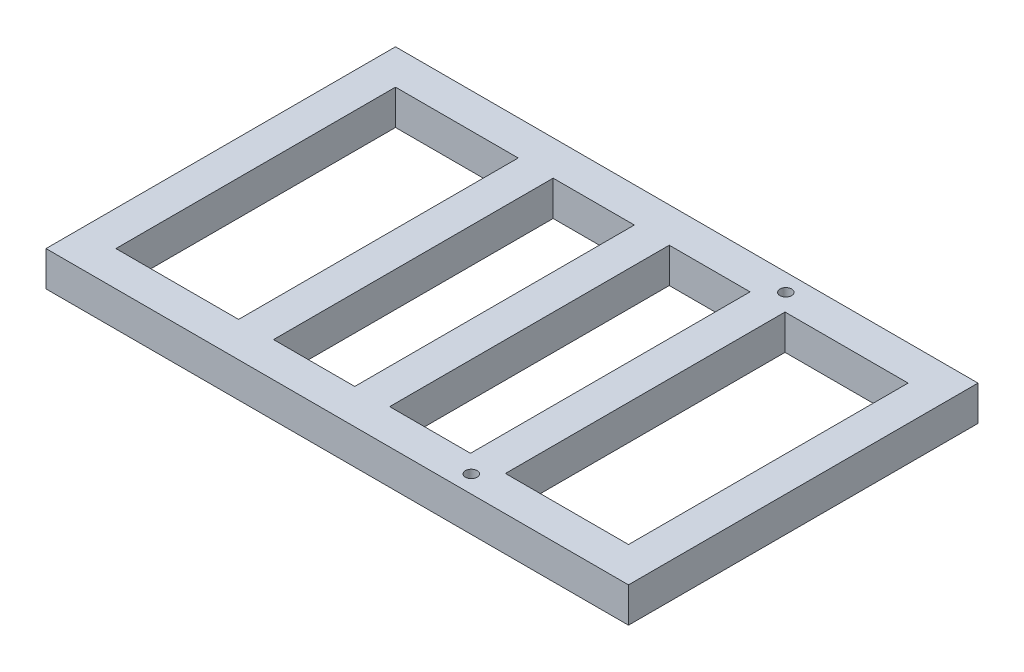
SolidWorks part; units mm, degrees
ref_plane "Front Plane" through (0, 0, 0) normal (0, 0, 1) x (1, 0, 0)
ref_plane "Top Plane" through (0, 0, 0) normal (0, 1, 0) x (1, 0, 0)
ref_plane "Right Plane" through (0, 0, 0) normal (1, 0, 0) x (0, 0, -1)
sketch "Sketch2" plane through (0, 0, 0) normal (0, 1, 0) x (1, 0, 0)
  line L0 (-55, 0) -> (55, 0) construction
  line L1 (-220, 120) -> (220, 120)
  line L2 (-220, 120) -> (-220, -120)
  line L3 (-220, -120) -> (220, -120)
  line L4 (220, 120) -> (220, -120)
  line L5 (-220, 120) -> (220, -120) construction
  line L6 (-220, -120) -> (220, 120) construction
  line L7 (0, -55) -> (0, 55) construction
  line L9 (-250, 150) -> (250, 150)
  line L10 (-250, 150) -> (-250, -150)
  line L11 (-250, -150) -> (250, -150)
  line L12 (250, 150) -> (250, -150)
  line L13 (-250, 150) -> (250, -150) construction
  line L14 (-250, -150) -> (250, 150) construction
  point P0 (0, 0)
  point P9 (0, 0)
  dimension "D1" = 30
  dimension "D2" = 30
  dimension "D3" = 30
  dimension "D4" = 30
  dimension "D5" = 500
  dimension "D6" = 300
extrude "Boss-Extrude1" add sketch "Sketch2" along normal blind 30
sketch "Sketch3" plane through (0, 30, 0) normal (0, 1, 0) x (1, 0, 0)
  line L0 (0, -16.5) -> (0, 16.5) construction
  line L1 (-15, 120) -> (15, 120)
  line L2 (-15, 120) -> (-15, -120)
  line L3 (-15, -120) -> (15, -120)
  line L4 (15, 120) -> (15, -120)
  line L5 (-15, 120) -> (15, -120) construction
  line L6 (-15, -120) -> (15, 120) construction
  line L7 (-16.5, 0) -> (16.5, 0) construction
  line L8 (-220, -120) -> (220, -120) construction
  point P0 (0, 0)
  dimension "D1" = 30
extrude "Boss-Extrude2" add sketch "Sketch3" against normal up to vertex (30 mm away) up to point (-250, 0, 150)
sketch "Sketch4" plane through (0, 30, 0) normal (0, 1, 0) x (1, 0, 0)
  line L0 (-16.5, 0) -> (16.5, 0) construction
  line L1 (-114.681, -120) -> (-84.681, -120)
  line L2 (-114.681, -120) -> (-114.681, 120)
  line L3 (-114.681, 120) -> (-84.681, 120)
  line L4 (-84.681, -120) -> (-84.681, 120)
  line L5 (-114.681, -120) -> (-84.681, 120) construction
  line L6 (-114.681, 120) -> (-84.681, -120) construction
  line L7 (-15, 120) -> (-220, 120) construction
  line L8 (220, 120) -> (15, 120) construction
  line L9 (84.3653, -120) -> (114.3653, -120)
  line L10 (84.3653, -120) -> (84.3653, 120)
  line L11 (84.3653, 120) -> (114.3653, 120)
  line L12 (114.3653, -120) -> (114.3653, 120)
  line L13 (84.3653, -120) -> (114.3653, 120) construction
  line L14 (84.3653, 120) -> (114.3653, -120) construction
  point P0 (-99.681, 0)
  point P9 (99.3653, 0)
  dimension "D1" = 30
  dimension "D2" = 30
sketch "Sketch7" plane through (0, 0, 0) normal (0, 1, 0) x (1, 0, 0)
extrude "Boss-Extrude3" add sketch "Sketch4" against normal up to vertex (30 mm away) up to point (-250, 0, 150)
sketch "Sketch8" plane through (0, 30, 0) normal (0, 1, 0) x (1, 0, 0)
  line L2 (250, 150) -> (-250, 150) construction
  circle A1 centre (100.0184, 135) radius 5
  dimension "D1" = 10
  dimension "D2" = 15
extrude "Cut-Extrude1" cut sketch "Sketch8" against normal blind 32
sketch "Sketch9" plane through (0, 30, 0) normal (0, 1, 0) x (1, 0, 0)
  line L0 (-250, -150) -> (250, -150) construction
  circle A0 centre (100.0604, -135) radius 5
  dimension "D1" = 10
  dimension "D2" = 15
extrude "Cut-Extrude2" cut sketch "Sketch9" against normal blind 34
